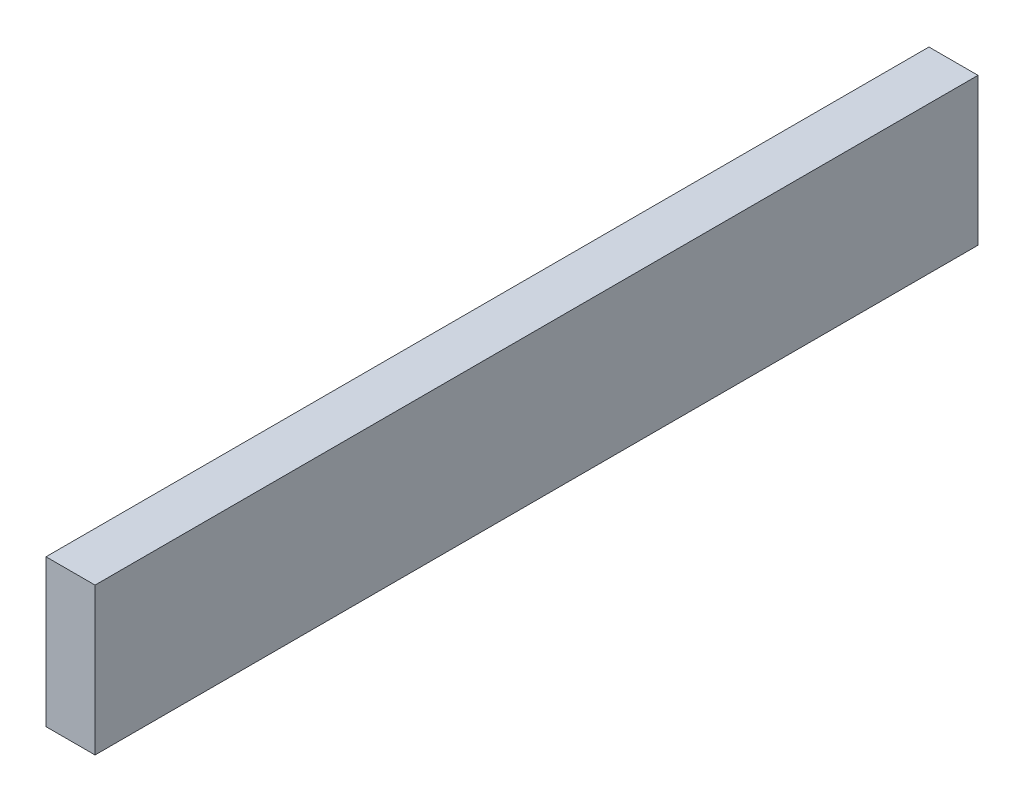
SolidWorks part; units mm, degrees
ref_plane "Front Plane" through (0, 0, 0) normal (1, 0, 0) x (0, 1, 0)
ref_plane "Top Plane" through (0, 0, 0) normal (0, 0, 1) x (0, 1, 0)
ref_plane "Right Plane" through (0, 0, 0) normal (0, 1, 0) x (-1, 0, 0)
sketch "Sketch1" plane through (0, 0, 0) normal (1, 0, 0) x (0, 1, 0)
  line L1 (0, 900) -> (300, 900)
  line L2 (0, 900) -> (0, -900)
  line L3 (0, -900) -> (300, -900)
  line L4 (300, 900) -> (300, -900)
  dimension "D1" = 1800
  dimension "D2" = 300
extrude "Boss-Extrude1" add sketch "Sketch1" along normal blind 50 and the other way blind 50
